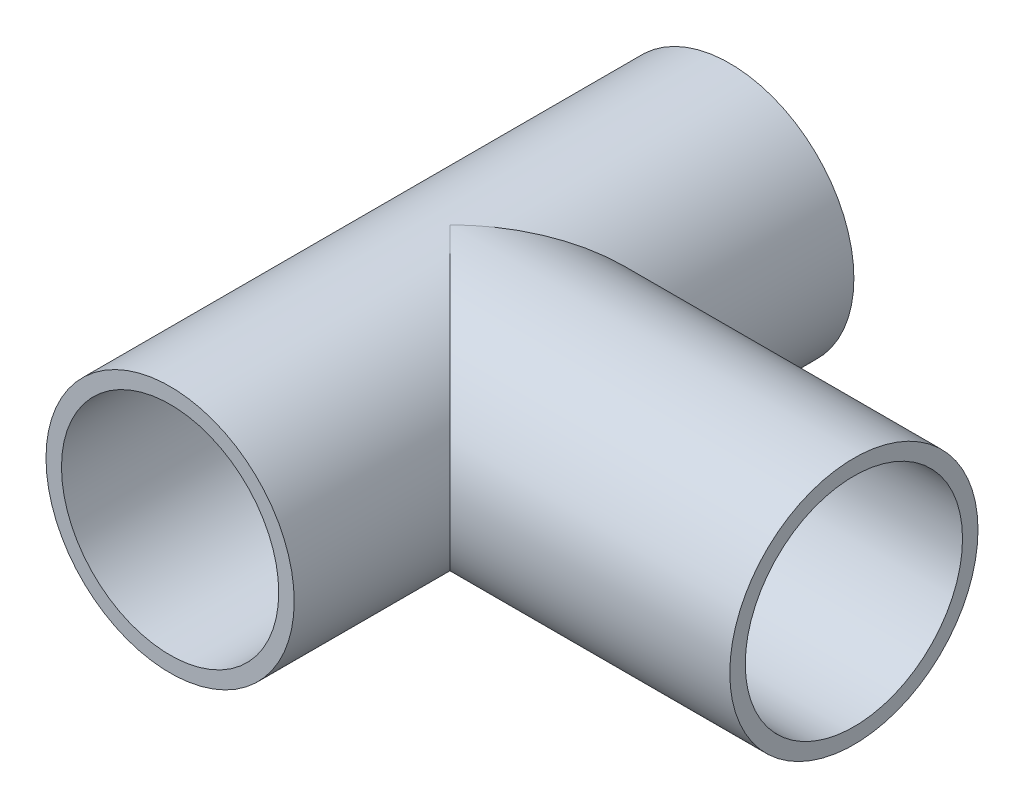
SolidWorks part; units mm, degrees
ref_plane "Front Plane" through (0, 0, 0) normal (0, 0, 1) x (1, 0, 0)
ref_plane "Top Plane" through (0, 0, 0) normal (0, 1, 0) x (1, 0, 0)
ref_plane "Right Plane" through (0, 0, 0) normal (1, 0, 0) x (0, 0, -1)
sketch "Through Section" plane through (0, 0, 0) normal (0, 0, 1) x (1, 0, 0)
  circle A0 centre (0, 0) radius 161.925
  circle A1 centre (0, 0) radius 141.732
  dimension "D1" = 283.464
  dimension "D2" = 323.85
extrude "Through Section Extrude" add sketch "Through Section" along normal blind 730.25
ref_plane "E Plane" through (527.05, 0, 0) normal (1, 0, 0) x (0, 0, -1)
sketch "Orthogonal Section OD" plane through (527.05, 0, 0) normal (1, 0, 0) x (0, 0, -1)
  line L1 (-730.25, -161.925) -> (0, -161.925) construction
  circle A0 centre (-365.125, 0) radius 161.925
  dimension "D3" = 323.85
  dimension "D1" = 365.125
  dimension "D2" = 161.925
extrude "Orthogonal Section OD Extrude" add sketch "Orthogonal Section OD" against normal up to surface (365.125 mm away) up to face at (161.925, 0, 730.25)
sketch "Orthogonal Section ID" plane through (527.05, 0, 0) normal (1, 0, 0) x (0, 0, -1)
  circle A0 centre (-365.125, 0) radius 141.732
  circle A1 centre (-365.125, 0) radius 161.925 construction
  point P3 (0, 0)
  dimension "D1" = 283.464
extrude "Orthogonal Section ID Cut" cut sketch "Orthogonal Section ID" against normal up to surface (527.05 mm away) up to plane "Right Plane"
equation "\"ID\"= 11.160in'EPG"
equation "\"OD\"= 12.75'EPG"
equation "\"A\"= 8in'EPG"
equation "\"C\" = 28.75in'EPG"
equation "\"E\"= 8in'EPG"
equation "\"D1@Through Section\" = \"ID\""
equation "\"D2@Through Section\" = \"OD\""
equation "\"D1@Through Section Extrude\" = \"C\""
equation "\"D1@Orthogonal Section OD\" = \"C\" / 2"
equation "\"D2@Orthogonal Section OD\" = \"OD\" / 2"
equation "\"D3@Orthogonal Section OD\" = \"OD\""
equation "\"D1@Orthogonal Section ID\" = \"ID\""
